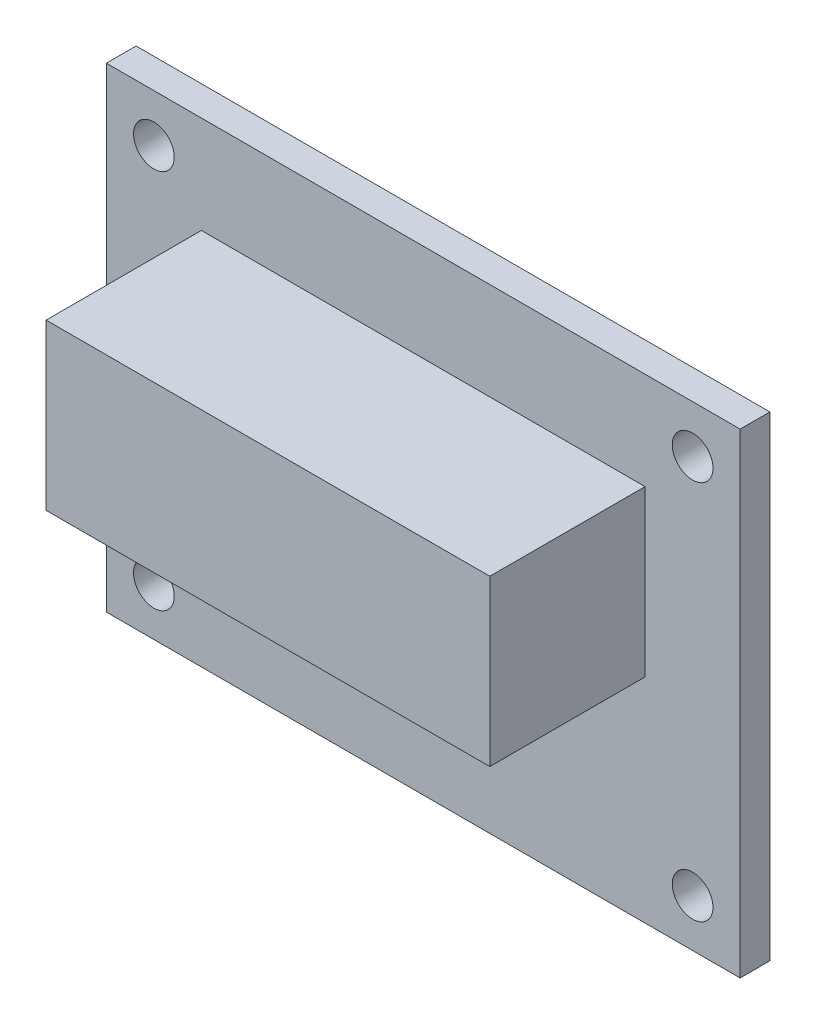
SolidWorks part; units mm, degrees
ref_plane "Front Plane" through (0, 0, 0) normal (0, 0, 1) x (1, 0, 0)
ref_plane "Top Plane" through (0, 0, 0) normal (0, 1, 0) x (1, 0, 0)
ref_plane "Right Plane" through (0, 0, 0) normal (1, 0, 0) x (0, 0, -1)
sketch "Sketch1" plane through (0, 0, 0) normal (0, 0, 1) x (1, 0, 0)
  line L1 (-25.4, -19.05) -> (25.4, -19.05)
  line L2 (-25.4, -19.05) -> (-25.4, 19.05)
  line L3 (-25.4, 19.05) -> (25.4, 19.05)
  line L4 (25.4, -19.05) -> (25.4, 19.05)
  line L5 (-25.4, -19.05) -> (25.4, 19.05) construction
  line L6 (-25.4, 19.05) -> (25.4, -19.05) construction
  point P0 (0, 0)
  dimension "D1" = 38.1
  dimension "D2" = 50.8
extrude "Boss-Extrude1" add sketch "Sketch1" along normal blind 2.3813
sketch "Sketch4" plane through (0, 0, 2.3813) normal (0, 0, 1) x (1, 0, 0)
  line L0 (-21.59, 19.05) -> (-21.59, 15.24) construction
  line L1 (25.4, 19.05) -> (-25.4, 19.05) construction
  line L2 (-21.59, 15.24) -> (-25.4, 15.24) construction
  line L3 (-25.4, 19.05) -> (-25.4, -19.05) construction
  dimension "D1" = 3.81
hole_wizard "#4 Clearance Hole1" positions "Sketch6" profile "Sketch5" hole size "#4" standard "ANSI Inch"
sketch "Sketch6" plane through (0, 0, 2.3813) normal (0, 0, 1) x (1, 0, 0)
  point P0 (-21.59, 15.24)
sketch "Sketch5" plane through (-21.59, 15.24, 2.3813) normal (1, 0, 0) x (0, -1, 0)
  line L0 (0, 0) -> (0, 4.1556)
  line L1 (0, 4.1556) -> (1.6319, 3.175)
  line L2 (1.6319, 3.175) -> (1.6319, 0)
  line L5 (1.6319, 0) -> (0, 0)
  line L10 (0, 4.1556) -> (-1.632, 3.175) construction
  line L11 (0, -6.35) -> (0, 107.95) construction
  dimension "Hole Dia." = 3.2639
  dimension "Hole Depth" = 3.175
  dimension "Drill Angle" = 118
mirror "Mirror1" about plane through (0, 0, 0) normal (1, 0, 0) of "#4 Clearance Hole1"
mirror "Mirror2" about plane through (0, 0, 0) normal (0, 1, 0) of "Mirror1"
sketch "Sketch2" plane through (0, 0, 2.3813) normal (0, 0, 1) x (1, 0, 0)
  line L1 (-17.78, -1.9604) -> (17.78, -1.9604)
  line L2 (-17.78, -1.9604) -> (-17.78, 11.2476)
  line L3 (-17.78, 11.2476) -> (17.78, 11.2476)
  line L4 (17.78, -1.9604) -> (17.78, 11.2476)
  line L5 (-17.78, -1.9604) -> (17.78, 11.2476) construction
  line L6 (-17.78, 11.2476) -> (17.78, -1.9604) construction
  point P0 (0, 4.6436)
  dimension "D1" = 35.56
  dimension "D2" = 13.208
extrude "Boss-Extrude2" add sketch "Sketch2" along normal blind 12.446
